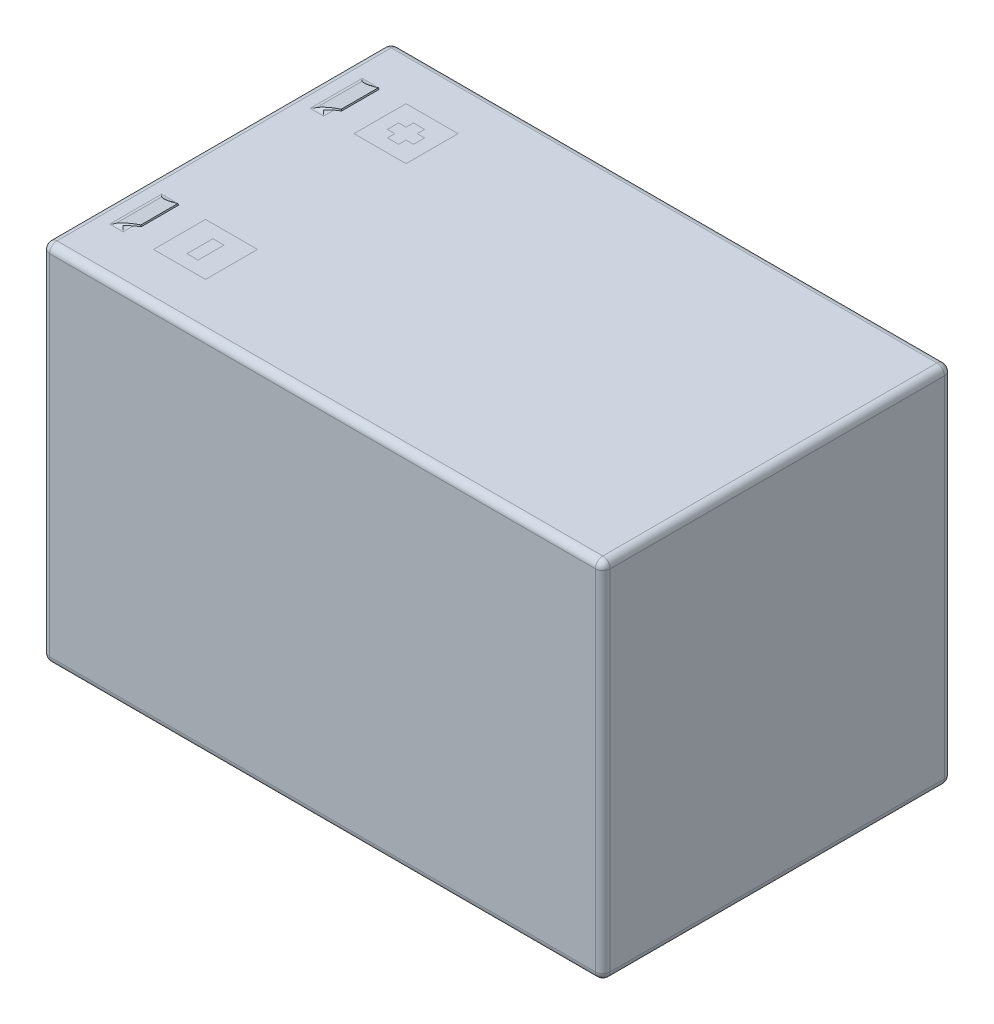
SolidWorks part; units mm, degrees
material "1023 Carbon Steel Sheet (SS)"
ref_plane "Front Plane" through (0, 0, 0) normal (0, 0, 1) x (1, 0, 0)
ref_plane "Top Plane" through (0, 0, 0) normal (0, 1, 0) x (1, 0, 0)
ref_plane "Right Plane" through (0, 0, 0) normal (1, 0, 0) x (0, 0, -1)
sketch "Sketch1" plane through (0, 0, 0) normal (0, 0, 1) x (1, 0, 0)
  line L1 (-75.5, 49) -> (75.5, 49)
  line L2 (-75.5, 49) -> (-75.5, -49)
  line L3 (-75.5, -49) -> (75.5, -49)
  line L4 (75.5, 49) -> (75.5, -49)
  line L5 (-75.5, 49) -> (75.5, -49) construction
  line L6 (-75.5, -49) -> (75.5, 49) construction
  point P0 (0, 0)
  dimension "D1" = 151
  dimension "D2" = 98
extrude "Boss-Extrude2" add sketch "Sketch1" along normal blind 94
sketch "Sketch2" plane through (0, 0, 0) normal (0, 0, -1) x (-1, 0, 0)
  line L0 (63.926, 51) -> (69.4394, 49.198)
  line L1 (69.4394, 49.198) -> (69.4394, 49)
  line L2 (-75.5, 49) -> (75.5, 49) construction
  line L3 (69.4394, 49) -> (67.7994, 49)
  line L4 (67.7994, 49) -> (67.7994, 49.3336)
  line L5 (67.7994, 49.3336) -> (63.8078, 50.6382)
  line L6 (63.8078, 50.6382) -> (63.926, 51)
  line L7 (75.5, -49) -> (-75.5, -49) construction
  dimension "D1" = 100
extrude "Boss-Extrude3" add sketch "Sketch2" against normal blind 10 from offset 15 offset against normal yes
ref_plane "Plane2" through (0, 0, 47) normal (0, 0, 1) x (1, 0, 0)
mirror "Mirror1" about plane through (0, 0, 47) normal (0, 0, 1) of "Boss-Extrude3"
sketch "Sketch4" plane through (0, 0, 0) normal (0, 0, -1) x (-1, 0, 0)
  text T0 "Battery" font "Century Gothic" height 10
split line "Split Line2"
fillet "Fillet1" radius 2 20 edges at (75.5, -49, 47) (75.5, 49, 47) (-68.6194, 49, 15) (-69.4394, 49, 20) (-68.6194, 49, 25) (-67.7994, 49, 20) (-68.6194, 49, 79) (-67.7994, 49, 74) (-68.6194, 49, 69) (-69.4394, 49, 74) (0, -49, 94) (0, 49, 94) (75.5, 0, 94) (-75.5, 49, 47) (-75.5, 0, 94) (-75.5, -49, 47) (0, 49, 0) (-75.5, 0, 0) (0, -49, 0) (75.5, 0, 0)
sketch "Sketch5" plane through (0, 49, 0) normal (0, 1, 0) x (1, 0, 0)
  line L0 (-73.5, -47) -> (111.1875, -47) construction
  line L1 (-58.5, -13) -> (-44.5, -13)
  line L2 (-58.5, -13) -> (-58.5, -27)
  line L3 (-58.5, -27) -> (-44.5, -27)
  line L4 (-44.5, -13) -> (-44.5, -27)
  line L5 (-73.5, -2) -> (-73.5, -92) construction
  line L6 (-58.5, -81) -> (-44.5, -81)
  line L7 (-58.5, -81) -> (-58.5, -67)
  line L8 (-58.5, -67) -> (-44.5, -67)
  line L9 (-44.5, -81) -> (-44.5, -67)
  line L10 (-51.5, -13) -> (-51.5, -10.1725) construction
  line L11 (-53, -16.5) -> (-50, -16.5)
  line L12 (-53, -16.5) -> (-53, -18.5)
  line L13 (-53, -23.5) -> (-50, -23.5)
  line L14 (-50, -16.5) -> (-50, -18.5)
  line L15 (-44.5, -20) -> (-39.2854, -20) construction
  line L16 (-50, -77.5) -> (-50, -70.5)
  line L17 (-53, -70.5) -> (-50, -70.5)
  line L18 (-53, -77.5) -> (-53, -70.5)
  line L19 (-53, -77.5) -> (-50, -77.5)
  line L20 (-53, -18.5) -> (-55, -18.5)
  line L21 (-48, -18.5) -> (-50, -18.5)
  line L22 (-48, -18.5) -> (-48, -21.5)
  line L23 (-48, -21.5) -> (-50, -21.5)
  line L24 (-55, -18.5) -> (-55, -21.5)
  line L25 (-53, -21.5) -> (-53, -23.5)
  line L26 (-53, -21.5) -> (-55, -21.5)
  line L27 (-50, -21.5) -> (-50, -23.5)
  point P20 (-51.5, -16.5)
  point P32 (-48, -20)
  dimension "D1" = 14
  dimension "D2" = 14
  dimension "D3" = 15
  dimension "D4" = 3
  dimension "D5" = 7
  dimension "D6" = 3
  dimension "D7" = 7
split line "Split Line3"
